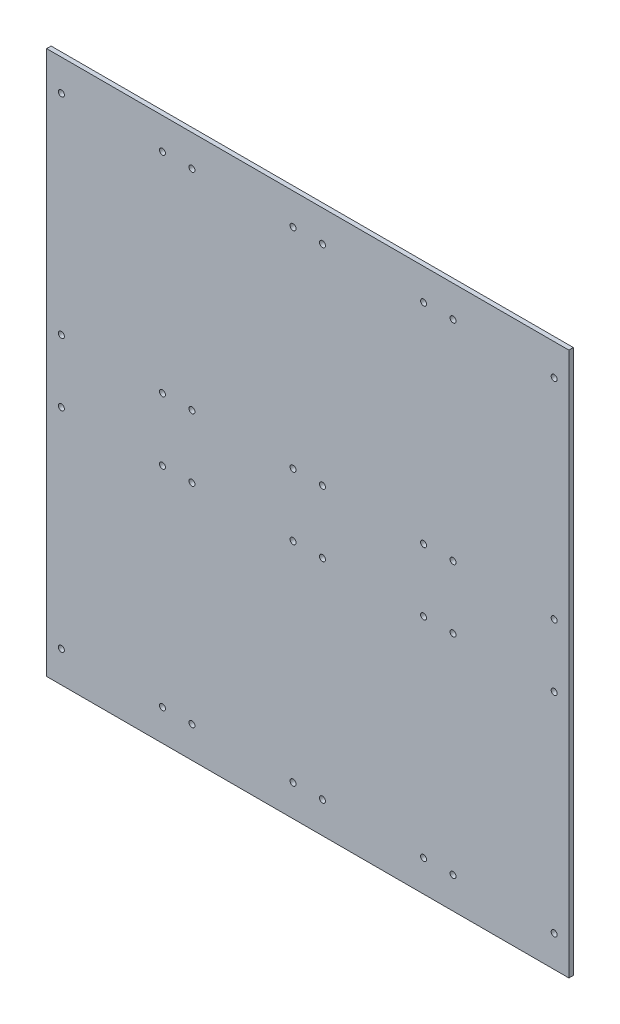
SolidWorks part; units mm, degrees
ref_plane "Front Plane" through (0, 0, 0) normal (0, 0, 1) x (1, 0, 0)
ref_plane "Top Plane" through (0, 0, 0) normal (0, 1, 0) x (1, 0, 0)
ref_plane "Right Plane" through (0, 0, 0) normal (1, 0, 0) x (0, 0, -1)
sketch "Sketch1" plane through (0, 0, 0) normal (0, 0, 1) x (1, 0, 0)
  line L0 (-16.92, 45.5) -> (-16.92, -45.5) construction
  line L1 (-21.85, 45.5) -> (21.85, 45.5)
  line L2 (-21.85, 45.5) -> (-21.85, -45.5)
  line L3 (-21.85, -45.5) -> (21.85, -45.5)
  line L4 (21.85, 45.5) -> (21.85, -45.5)
  line L5 (-21.85, 45.5) -> (21.85, -45.5) construction
  line L6 (-21.85, -45.5) -> (21.85, 45.5) construction
  line L7 (0, 45.5) -> (0, -45.5) construction
  line L8 (16.92, 45.5) -> (16.92, -45.5) construction
  line L9 (-21.85, 0) -> (21.85, 0) construction
  circle A0 centre (-16.92, 35) radius 1
  circle A1 centre (16.92, 35) radius 1
  circle A2 centre (16.92, -35) radius 1
  circle A3 centre (-16.92, -35) radius 1
  point P0 (0, 0)
  dimension "D5" = 2
  dimension "D1" = 91
  dimension "D2" = 43.7
  dimension "D3" = 4.93
  dimension "D4" = 10.5
extrude "Boss-Extrude1" add sketch "Sketch1" along normal blind 1.5
pattern_linear "LPattern1" count 4 spacing 43.7 along (-1, 0, 0) count 2 spacing 91 along (0, 1, 0) of "Boss-Extrude1"
